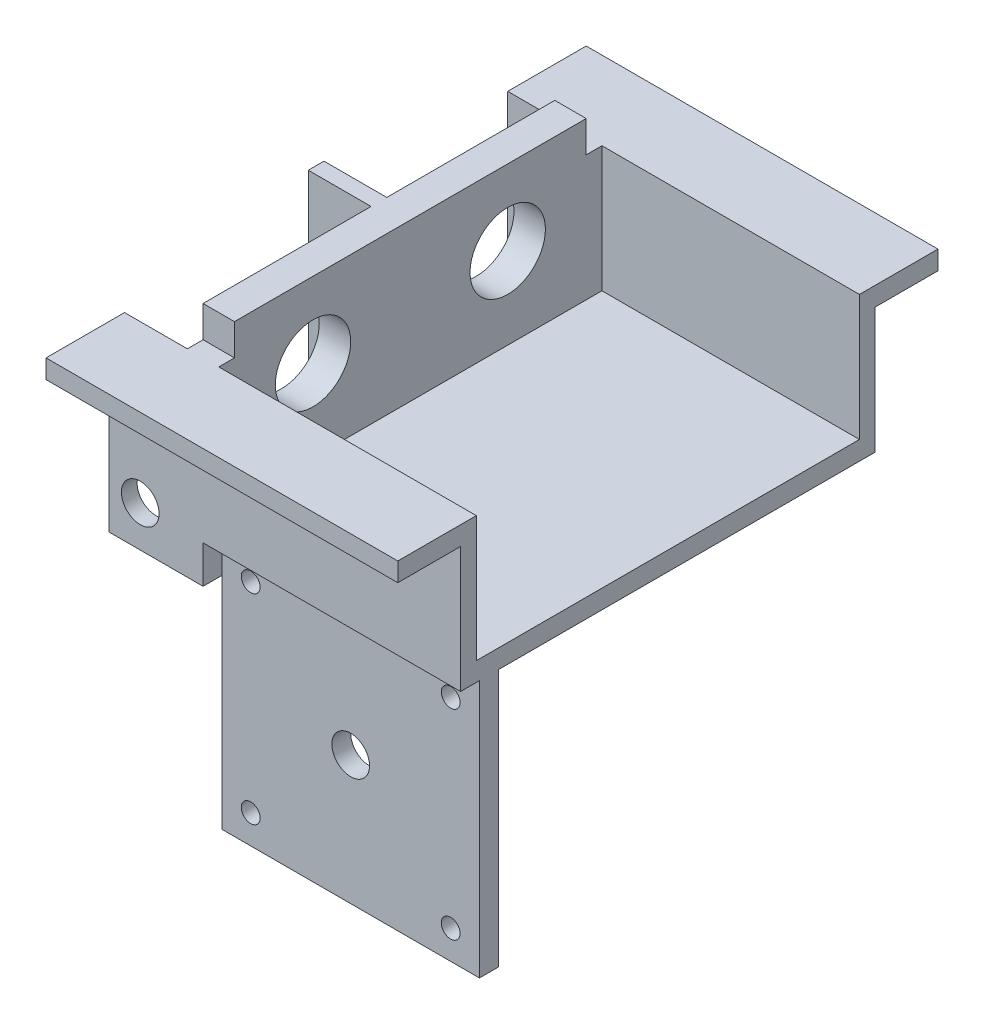
SolidWorks part; units mm, degrees
material "ABS"
ref_plane "Front Plane" through (0, 0, 0) normal (0, 0, 1) x (1, 0, 0)
ref_plane "Top Plane" through (0, 0, 0) normal (0, 1, 0) x (1, 0, 0)
ref_plane "Right Plane" through (0, 0, 0) normal (1, 0, 0) x (0, 0, -1)
sketch "Sketch1" plane through (0, 0, 0) normal (1, 0, 0) x (0, 0, -1)
  line L0 (-28, 12) -> (-3, -12) construction
  line L1 (-28, -12) -> (28, -12) construction
  line L2 (-28, -12) -> (-28, 12) construction
  line L3 (-28, 12) -> (28, 12)
  line L4 (28, -12) -> (28, 12) construction
  line L5 (-28, -12) -> (28, 12) construction
  line L6 (-28, 12) -> (28, -12) construction
  line L7 (-3, 12) -> (-3, -12) construction
  line L8 (3, 12) -> (3, -12) construction
  line L9 (-28, -12) -> (-3, 12) construction
  line L10 (3, 12) -> (28, -12) construction
  line L11 (3, -12) -> (28, 12) construction
  line L12 (-1.25, 12) -> (-1.25, -22)
  line L13 (-1.25, -22) -> (-3, 12) construction
  line L14 (1.25, 12) -> (1.25, -22)
  line L15 (1.25, -22) -> (3, 12) construction
  line L16 (-43, 7) -> (-28, 7)
  line L17 (-43, 7) -> (-43, 4)
  line L18 (-43, 4) -> (-33, 4)
  line L19 (43, 7) -> (28, 7)
  line L20 (43, 7) -> (43, 4)
  line L21 (43, 4) -> (33, 4)
  line L22 (-33, -22) -> (33, -22)
  line L23 (-33, 4) -> (-30.5, 4) construction
  line L24 (-30.5, 4) -> (-30.5, -22)
  line L25 (33, 4) -> (30.5, 4) construction
  line L26 (30.5, 4) -> (30.5, -22)
  line L27 (28, 7) -> (28, 12)
  line L28 (-30.5, 4) -> (-30.5, 7)
  line L29 (-33, -13) -> (33, -13)
  line L30 (-33, -16) -> (33, -16)
  line L31 (-28, 7) -> (-28, 12)
  line L32 (-33, 4) -> (-33, -22)
  line L33 (30.5, 4) -> (30.5, 7)
  line L35 (33, -22) -> (33, 4)
  circle A0 centre (-15.5, 0) radius 6
  circle A1 centre (15.5, 0) radius 6
  circle A2 centre (-15.5, 0) radius 12.5 construction
  circle A3 centre (15.5, 0) radius 12.5 construction
  point P0 (0, 0)
  dimension "D4" = 12
  dimension "D6" = 25
  dimension "D1" = 56
  dimension "D2" = 24
  dimension "D3" = 6
  dimension "D5" = 2.5
  dimension "D7" = 3
  dimension "D9" = 5
  dimension "D10" = 34
  dimension "D11" = 2.5
  dimension "D12" = 3
  dimension "D13" = 28
  dimension "D8" = 19
  dimension "D14" = 15
extrude "Boss-Extrude1" add sketch "Sketch1" along normal blind 5 contours L2 L1 L12 L3 A0 | L4 L3 L14 L1 A1 | L14 L3 L12 L1 | L30 L12 L22 L14 | L30 L24 L22 L12 | L30 L14 L22 L26 | L30 L32 L22 L24 | L22 L35 L30 L26 region at (0, 11.6152, 14.625) region at (0, -0.5, 0) region at (0, 11.6152, -14.625) region at (0, -19, 0) region at (0, -19, 15.875) region at (0, -19, -15.875) region at (0, -19, 31.75) region at (0, -19, -31.75)
extrude "Boss-Extrude2" add sketch "Sketch1<4>" against normal blind 10 contours L14 L3 L12 L1 | L23 L32 L22 L24 | L22 L35 L25 L26 | L12 L30 L14 L29 | L30 L12 L22 L14 | L18 L32 L29 L24 L17 | L29 L32 L30 L24 | L30 L35 L29 L26 | L29 L35 L21 L20 L26 region at (0, -0.5, 0) region at (0, -14.5, 0) region at (0, 5.5, 30.7358) region at (0, -19, 0) region at (0, -14.5, 31.75) region at (0, -14.5, -31.75) region at (0, -4.5, -30.7358) region at (0, -19, 31.75) region at (0, -19, -31.75)
sketch "Sketch1<4>" plane through (0, 0, 0) normal (1, 0, 0) x (0, 0, -1) same geometry as "Sketch1"
sketch "Sketch2" plane through (0, 0, 1.25) normal (0, 0, 1) x (1, 0, 0)
  line L0 (-5, 12) -> (-5, -22) construction
  line L1 (-10, 12) -> (0, 12) construction
  line L2 (-10, -22) -> (0, -22) construction
  line L3 (-10, 0) -> (0, 0) construction
  line L4 (-10, 12) -> (-10, -22) construction
  line L5 (0, 12) -> (0, -13) construction
  line L6 (0, -12.5) -> (-10, -12.5) construction
  circle A0 centre (-5, -15.5) radius 3
  dimension "D1" = 6
  dimension "D2" = 12
  dimension "D3" = 12.5
extrude "Cut-Extrude1" cut sketch "Sketch2" against normal through all both and the other way through all
extrude "Boss-Extrude3" add sketch "Sketch1<6>" along normal blind 46 contours L29 L32 L30 L24 | L24 L30 L12 L29 | L12 L30 L14 L29 | L14 L30 L26 L29 | L30 L35 L29 L26 | L18 L32 L29 L24 L17 | L29 L35 L21 L20 L26 region at (0, -14.5, 0) region at (0, -14.5, 15.875) region at (0, 5.5, 30.7358) region at (0, -14.5, -15.875) region at (0, -14.5, 31.75) region at (0, -14.5, -31.75) region at (0, -4.5, -30.7358)
sketch "Sketch1<6>" plane through (0, 0, 0) normal (1, 0, 0) x (0, 0, -1) same geometry as "Sketch1"
sketch "Sketch3" plane through (0, -16, 0) normal (0, -1, 0) x (1, 0, 0)
  line L0 (46, 33) -> (46, -33) construction
  line L1 (5, 30) -> (46, 30)
  line L2 (5, 30) -> (5, 27)
  line L3 (5, 27) -> (46, 27)
  line L4 (46, 30) -> (46, 27)
  line L5 (46, 33) -> (5, 33) construction
  line L6 (5, 33) -> (5, -33) construction
  dimension "D1" = 3
  dimension "D2" = 3
extrude "Boss-Extrude4" add sketch "Sketch3" along normal blind 41
sketch "Sketch4" plane through (0, 0, 27) normal (0, 0, -1) x (-1, 0, 0)
  line L0 (-46, -16) -> (-5, -57) construction
  line L1 (-46, -57) -> (-5, -16) construction
  line L3 (-41.42, -52.42) -> (-9.58, -52.42) construction
  line L4 (-41.42, -52.42) -> (-41.42, -20.58) construction
  line L5 (-41.42, -20.58) -> (-9.58, -20.58) construction
  line L6 (-9.58, -52.42) -> (-9.58, -20.58) construction
  line L7 (-41.42, -52.42) -> (-9.58, -20.58) construction
  line L8 (-41.42, -20.58) -> (-9.58, -52.42) construction
  circle A0 centre (-25.5, -36.5) radius 3
  circle A1 centre (-41.42, -20.58) radius 1.5
  circle A2 centre (-9.58, -20.58) radius 1.5
  circle A3 centre (-9.58, -52.42) radius 1.5
  circle A4 centre (-41.42, -52.42) radius 1.5
  point P8 (-25.5, -36.5)
  dimension "D2" = 3
  dimension "D3" = 6
  dimension "D1" = 31.84
extrude "Cut-Extrude2" cut sketch "Sketch4" against normal up to surface (6 mm away) up to face at (13.6667, -11.3333, 33)
equation "\"CarriageWidth\"= 56"
equation "\"D1@Sketch1\"=\"CarriageWidth\""
equation "\"StrutWidth\"=15"
equation "\"D3@Sketch2\"=\"ScrewCogDiameter\"/2"
equation "\"D14@Sketch1\"=\"StrutWidth\""
equation "\"ScrewCogDiameter\"=25"
equation "\"D6@Sketch1\"=\"ScrewCogDiameter\""
equation "\"WormDiameter\"=6"
equation "\"D1@Sketch2\"=\"WormDiameter\""
